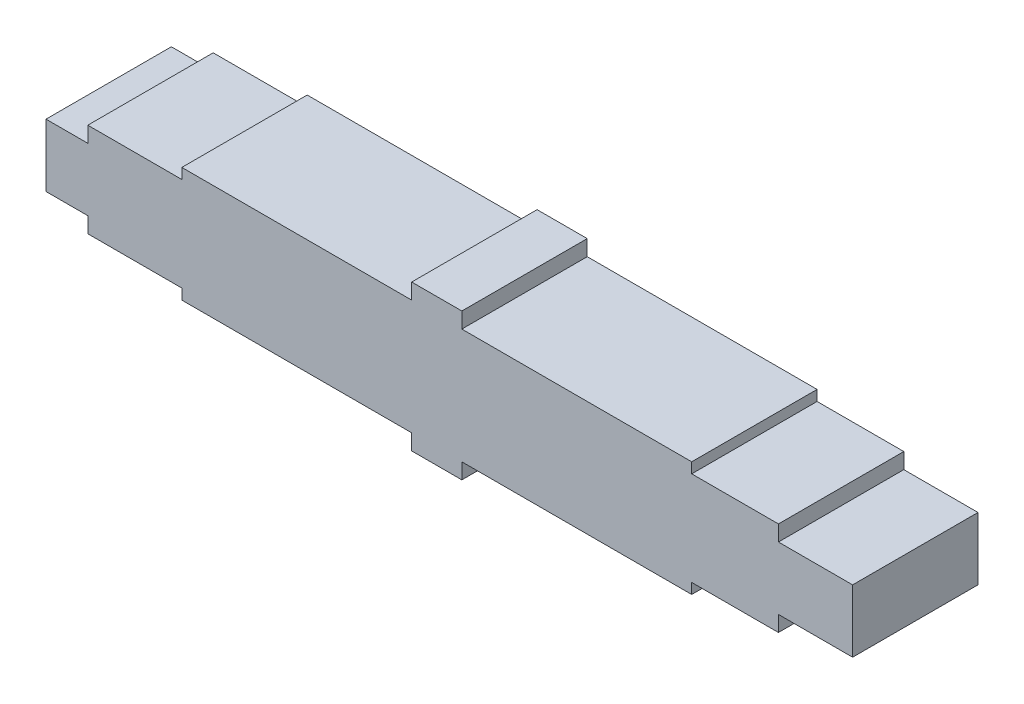
SolidWorks part; units mm, degrees
material "1.0553 (S355J0)"
ref_plane "Front Plane" through (0, 0, 0) normal (0, 0, 1) x (1, 0, 0)
ref_plane "Top Plane" through (0, 0, 0) normal (0, 1, 0) x (1, 0, 0)
ref_plane "Right Plane" through (0, 0, 0) normal (1, 0, 0) x (0, 0, -1)
sketch "Sketch1" plane through (0, 0, 0) normal (0, 0, 1) x (1, 0, 0)
  line L0 (-721.8464, 0) -> (35370.4735, 0) construction
  line L1 (0, 0) -> (-12, 0)
  line L2 (-12, -15) -> (-12, 15)
  line L3 (-12, 15) -> (8, 15)
  line L4 (8, 15) -> (8, 22.5)
  line L5 (8, 22.5) -> (53, 22.5)
  line L6 (53, 22.5) -> (53, 27.5)
  line L7 (53, 27.5) -> (163, 27.5)
  line L8 (163, 27.5) -> (163, 35)
  line L9 (163, 35) -> (187, 35)
  line L10 (187, 35) -> (187, 27.5)
  line L11 (187, 27.5) -> (297, 27.5)
  line L12 (297, 27.5) -> (297, 22.5)
  line L13 (297, 22.5) -> (338.5, 22.5)
  line L14 (338.5, 22.5) -> (338.5, 15)
  line L15 (338.5, 15) -> (374, 15)
  line L16 (374, 15) -> (374, -15)
  line L18 (338.5, -15) -> (374, -15)
  line L19 (338.5, -22.5) -> (338.5, -15)
  line L20 (297, -22.5) -> (338.5, -22.5)
  line L21 (297, -27.5) -> (297, -22.5)
  line L22 (187, -27.5) -> (297, -27.5)
  line L23 (187, -35) -> (187, -27.5)
  line L24 (163, -35) -> (187, -35)
  line L25 (163, -27.5) -> (163, -35)
  line L26 (53, -27.5) -> (163, -27.5)
  line L27 (53, -22.5) -> (53, -27.5)
  line L28 (8, -22.5) -> (53, -22.5)
  line L29 (8, -15) -> (8, -22.5)
  line L30 (-12, -15) -> (8, -15)
  dimension "D1" = 30
  dimension "D2" = 45
  dimension "D3" = 55
  dimension "D4" = 70
  dimension "D5" = 55
  dimension "D6" = 45
  dimension "D7" = 30
  dimension "D8" = 24
  dimension "D9" = 20
  dimension "D10" = 45
  dimension "D11" = 110
  dimension "D12" = 35.5
  dimension "D13" = 41.5
  dimension "D14" = 110
  dimension "D16" = 8
extrude "Boss-Extrude1" add sketch "Sketch1" along normal blind 30 and the other way blind 30 contours L7 L8 L9 L10 L11 L12 L13 L14 L15 L16 L18 L19 L20 L21 L22 L23 L24 L25 L26 L27 L28 L29 L30 L2 L3 L4 L5 L6
sketch "Sketch3" plane through (0, 0, 0) normal (0, 0, 1) x (1, 0, 0)
  line L0 (-1000, 0) -> (49000, 0) construction
  line L1 (108, 22.4953) -> (108, 23.6179)
  line L2 (242, 25.3863) -> (242, 26.4996)
  line L3 (0, 0) -> (350, 0)
  spline S0 degree 4 poles (0, 0) (-0.0004, 0.1203) (-0.0003, 0.3608) (0.0023, 0.842) (0.0229, 1.5202) (0.0896, 2.2429) (0.2367, 2.9865) (0.4362, 3.6222) (0.6873, 4.199) (1.0029, 4.7547) (1.4079, 5.3197) (1.9396, 5.9172) (2.6586, 6.5731) (3.6779, 7.3273) (5.1788, 8.218) (7.5001, 9.3075) (11.351, 10.704) (16.9997, 12.2362) (24.2365, 13.7424) (32.6661, 15.1493) (41.4869, 16.3863) (49.2237, 17.3301) (55.8626, 18.0664) (61.4008, 18.64) (65.8308, 19.0774) (70.268, 19.4961) (74.6972, 19.8971) (79.1442, 20.2838) (83.5641, 20.6546) (87.4782, 20.9709) (90.7608, 21.2296) (93.6109, 21.4485) (95.6979, 21.6075) (98.7244, 21.8321) (101.588, 22.0433) (106.5833, 22.3981) (110.2142, 22.6494) (115.2784, 22.9924) (117.1818, 23.1148) (118.8882, 23.2275) knots 0 0 0 0 0 0.003838 0.007675 0.015351 0.021647 0.026958 0.031813 0.036568 0.041681 0.047311 0.053953 0.062039 0.072679 0.087699 0.10955 0.143737 0.203218 0.274262 0.345307 0.416351 0.487395 0.522917 0.558439 0.593962 0.629484 0.665006 0.700528 0.73605 0.771572 0.789333 0.807094 0.824855 0.842616 0.878138 0.913661 0.95683 1 1 1 1 1 construction
  spline S1 degree 4 poles (0, 0) (-0.0004, 0.1203) (-0.0003, 0.3608) (0.0023, 0.842) (0.0229, 1.5202) (0.0896, 2.2429) (0.2367, 2.9865) (0.4362, 3.6222) (0.6873, 4.199) (1.0029, 4.7547) (1.4079, 5.3197) (1.9396, 5.9172) (2.6586, 6.5731) (3.6779, 7.3273) (5.1788, 8.218) (7.5001, 9.3075) (11.351, 10.704) (16.9997, 12.2362) (24.2365, 13.7424) (32.6661, 15.1493) (41.4869, 16.3863) (49.2237, 17.3301) (55.8626, 18.0664) (61.4008, 18.64) (65.8308, 19.0774) (70.268, 19.4961) (74.6972, 19.8971) (79.1442, 20.2838) (83.5641, 20.6546) (87.4782, 20.9709) (90.7608, 21.2296) (93.6109, 21.4485) (95.6979, 21.6075) (98.7244, 21.8321) (101.588, 22.0433) (104.9493, 22.282) (106.9852, 22.4248) (108, 22.4953) knots 0 0 0 0 0 0.003838 0.007675 0.015351 0.021647 0.026958 0.031813 0.036568 0.041681 0.047311 0.053953 0.062039 0.072679 0.087699 0.10955 0.143737 0.203218 0.274262 0.345307 0.416351 0.487395 0.522917 0.558439 0.593962 0.629484 0.665006 0.700528 0.73605 0.771572 0.789333 0.807094 0.824855 0.842616 0.878138 0.913661 0.913661 0.913661 0.913661 0.913661
  spline S2 degree 4 poles (231.1963, 26.2061) (231.5948, 26.1765) (232.0837, 26.1413) (233.7676, 26.0151) (235.9112, 25.8566) (240.2975, 25.5203) (243.3462, 25.2822) (248.3142, 24.8842) (251.0978, 24.6526) (254.0963, 24.402) (256.116, 24.2284) (258.3954, 24.0315) (260.5235, 23.8435) (263.273, 23.5976) (267.6177, 23.1996) (272.5306, 22.7316) (277.9692, 22.1868) (284.5021, 21.4958) (289.938, 20.8865) (295.3724, 20.2376) (301.8846, 19.4012) (308.389, 18.4988) (315.9596, 17.3264) (324.3087, 15.8028) (331.5226, 14.1826) (337.2704, 12.5347) (341.3141, 11.0192) (343.8395, 9.8216) (345.5574, 8.8028) (346.7409, 7.9365) (347.5948, 7.1714) (348.2273, 6.4796) (348.723, 5.8139) (349.119, 5.147) (349.441, 4.4417) (349.6997, 3.6509) (349.8872, 2.736) (349.9715, 1.8482) (349.9972, 1.021) (350.0003, 0.4375) (350.0004, 0.1458) (350, 0) knots 0 0 0 0 0 0.010692 0.021385 0.04277 0.08554 0.120111 0.154683 0.171968 0.189254 0.20654 0.223826 0.241111 0.258397 0.292969 0.362112 0.396683 0.431255 0.500398 0.534969 0.569541 0.638684 0.707827 0.77697 0.837595 0.872166 0.89655 0.913251 0.925776 0.935171 0.942809 0.949414 0.955339 0.961346 0.967266 0.973858 0.98157 0.990785 0.995392 1 1 1 1 1 construction
  spline S3 degree 4 poles (242, 25.3863) (242.9977, 25.3082) (244.9908, 25.1505) (248.3142, 24.8842) (251.0978, 24.6526) (254.0963, 24.402) (256.116, 24.2284) (258.3954, 24.0315) (260.5235, 23.8435) (263.273, 23.5976) (267.6177, 23.1996) (272.5306, 22.7316) (277.9692, 22.1868) (284.5021, 21.4958) (289.938, 20.8865) (295.3724, 20.2376) (301.8846, 19.4012) (308.389, 18.4988) (315.9596, 17.3264) (324.3087, 15.8028) (331.5226, 14.1826) (337.2704, 12.5347) (341.3141, 11.0192) (343.8395, 9.8216) (345.5574, 8.8028) (346.7409, 7.9365) (347.5948, 7.1714) (348.2273, 6.4796) (348.723, 5.8139) (349.119, 5.147) (349.441, 4.4417) (349.6997, 3.6509) (349.8872, 2.736) (349.9715, 1.8482) (349.9972, 1.021) (350.0003, 0.4375) (350.0004, 0.1458) (350, 0) knots 0.08554 0.08554 0.08554 0.08554 0.08554 0.120111 0.154683 0.171968 0.189254 0.20654 0.223826 0.241111 0.258397 0.292969 0.362112 0.396683 0.431255 0.500398 0.534969 0.569541 0.638684 0.707827 0.77697 0.837595 0.872166 0.89655 0.913251 0.925776 0.935171 0.942809 0.949414 0.955339 0.961346 0.967266 0.973858 0.98157 0.990785 0.995392 1 1 1 1 1
  spline S4 degree 4 poles (94.5643, 23.3395) (94.9651, 23.3477) (95.7447, 23.3637) (97.0832, 23.3911) (100.0604, 23.4526) (102.217, 23.4971) (106.9287, 23.5955) (108.9982, 23.6388) (114.0027, 23.7441) (117.5245, 23.8187) (122.6241, 23.9271) (127.3862, 24.029) (133.517, 24.1605) (140.6696, 24.3148) (149.244, 24.5004) (158.9333, 24.7108) (169.004, 24.9298) (178.9458, 25.146) (189.0593, 25.3655) (198.9131, 25.5789) (209.1881, 25.8004) (218.2436, 25.9949) (227.1815, 26.1855) (233.1914, 26.3134) (240.9814, 26.4782) (244.164, 26.5453) (251.592, 26.7016) (253.0765, 26.7323) (255.6437, 26.7862) knots 0 0 0 0 0 0.008911 0.017821 0.039658 0.061495 0.083332 0.104088 0.126568 0.157701 0.188835 0.219968 0.251101 0.306857 0.369123 0.43139 0.493656 0.555923 0.618189 0.680456 0.742722 0.804988 0.854401 0.885534 0.916667 0.958083 1 1 1 1 1 construction
  spline S5 degree 4 poles (108, 23.6179) (108.6953, 23.6325) (110.1341, 23.6627) (114.0027, 23.7441) (117.5245, 23.8187) (122.6241, 23.9271) (127.3862, 24.029) (133.517, 24.1605) (140.6696, 24.3148) (149.244, 24.5004) (158.9333, 24.7108) (169.004, 24.9298) (178.9458, 25.146) (189.0593, 25.3655) (198.9131, 25.5789) (209.1881, 25.8004) (218.2436, 25.9949) (227.1815, 26.1855) (233.1914, 26.3134) (238.874, 26.4336) (240.957, 26.4776) (242, 26.4996) knots 0.083332 0.083332 0.083332 0.083332 0.083332 0.104088 0.126568 0.157701 0.188835 0.219968 0.251101 0.306857 0.369123 0.43139 0.493656 0.555923 0.618189 0.680456 0.742722 0.804988 0.854401 0.885534 0.916667 0.916667 0.916667 0.916667 0.916667
  dimension "D1" = 350
  dimension "D2" = 44.9905
  dimension "D3" = 50.7727
  dimension "D4" = 47.2358
  dimension "D5" = 52.9993
revolve "Cut-Revolve2" cut sketch "Sketch3" angle 360 about L0
